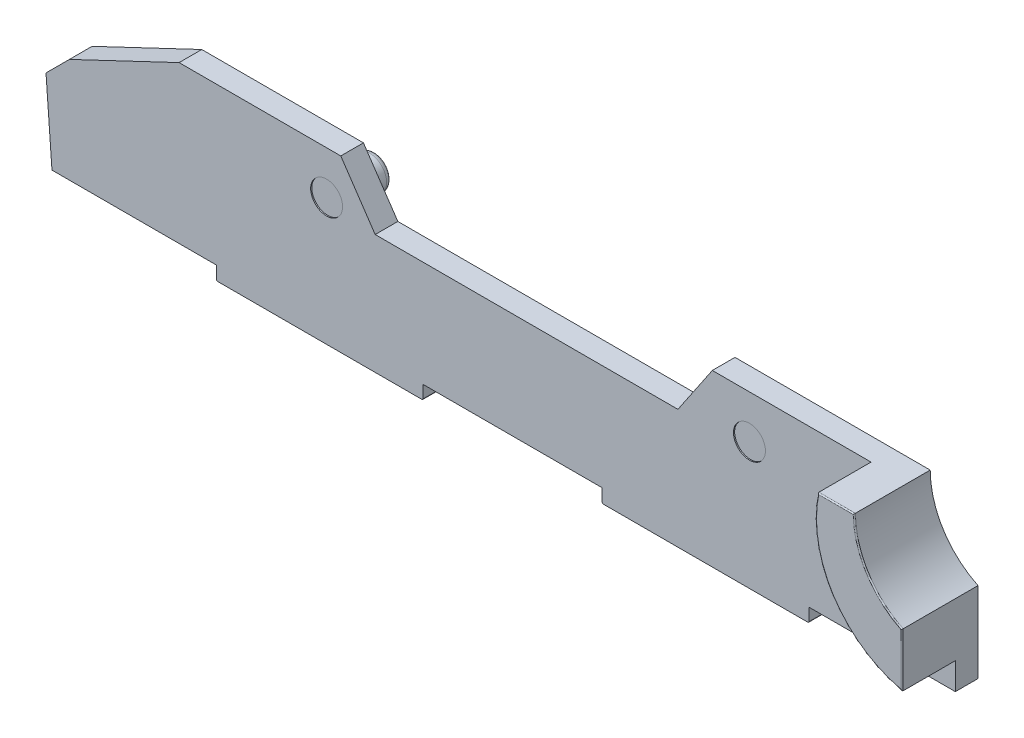
SolidWorks part; units mm, degrees
ref_plane "Front Plane" through (0, 0, 0) normal (0, 0, 1) x (1, 0, 0)
ref_plane "Top Plane" through (0, 0, 0) normal (0, 1, 0) x (1, 0, 0)
ref_plane "Right Plane" through (0, 0, 0) normal (1, 0, 0) x (0, 0, -1)
sketch "Sketch1" plane through (0, 0, 0) normal (0, 0, 1) x (1, 0, 0)
  line L1 (0, 0) -> (79.73, 0)
  line L2 (0, 0) -> (-0.5269, 7.1672)
  line L3 (-0.5269, 7.1672) -> (1.5378, 9.2319)
  line L4 (1.5378, 9.2319) -> (11.22, 13.83)
  line L5 (25.49, 0) -> (25.49, 13.83) construction
  line L6 (25.49, 13.83) -> (11.22, 13.83)
  line L7 (0, 0) -> (0, 10.43) construction
  line L9 (15.389, 13.83) -> (15.389, 9.34) construction
  line L10 (25.49, 13.83) -> (28.5258, 9.34)
  line L11 (15.389, 9.34) -> (39.4066, 9.34) construction
  line L12 (55.2458, 9.34) -> (58.2817, 13.83)
  line L13 (25.49, 13.83) -> (63.2386, 13.83) construction
  line L14 (58.2817, 13.83) -> (75.5117, 13.83)
  line L15 (79.73, 0) -> (79.73, 7.11)
  line L16 (28.5258, 9.34) -> (55.2458, 9.34)
  arc A0 (75.5117, 13.83) -> (79.73, 7.11) centre (82.9735, 13.83) ccw
  dimension "D1" = 79.73
  dimension "D2" = 2.92
  dimension "D4" = 5.42
  dimension "D5" = 13.83
  dimension "D6" = 25.49
  dimension "D7" = 14.27
  dimension "D8" = 10.43
  dimension "D9" = 26.72
  dimension "D10" = 5.42
  dimension "D11" = 17.23
  dimension "D12" = 7.11
  dimension "D13" = 4.49
extrude "Boss-Extrude1" add sketch "Sketch1" along normal blind 2
sketch "Sketch2" plane through (0, 0, 0) normal (0, -1, 0) x (1, 0, 0)
  line L0 (0, 2) -> (14.5, 2) construction
  line L1 (0, 2) -> (79.73, 2) construction
  line L2 (14.5, 2) -> (32.75, 2)
  line L3 (14.5, 2) -> (14.5, 0.8)
  line L4 (32.75, 2) -> (32.75, 0.8)
  line L5 (32.75, 0.8) -> (14.5, 0.8)
  dimension "D1" = 14.5
  dimension "D2" = 18.25
  dimension "D3" = 1.2
extrude "Boss-Extrude2" add sketch "Sketch2" along normal blind 1.2
sketch "Sketch3" plane through (0, 0, 0) normal (0, -1, 0) x (1, 0, 0)
  line L1 (32.75, 2) -> (79.73, 2) construction
  line L3 (48.56, 2) -> (66.81, 2)
  line L4 (48.56, 2) -> (48.56, 0.8)
  line L5 (66.81, 2) -> (66.81, 0.8)
  line L6 (66.81, 0.8) -> (48.56, 0.8)
  dimension "D2" = 18.25
  dimension "D3" = 1.2
extrude "Boss-Extrude3" add sketch "Sketch3" along normal blind 1.2
fillet "Fillet1" radius 0.1 1 edges at (66.81, -1.2, 1.4)
fillet "Fillet2" radius 0.1 1 edges at (48.56, -1.2, 1.4)
fillet "Fillet3" radius 0.1 1 edges at (32.75, -1.2, 1.4)
fillet "Fillet4" radius 0.1 1 edges at (14.5, -1.2, 1.4)
sketch "Sketch4" plane through (0, 0, 2) normal (0, 0, 1) x (1, 0, 0)
  line L0 (25.49, 13.83) -> (11.22, 13.83) construction
  line L1 (28.5258, 9.34) -> (25.49, 13.83) construction
  line L2 (75.5117, 13.83) -> (58.2817, 13.83) construction
  line L3 (58.2817, 13.83) -> (55.2458, 9.34) construction
  circle A0 centre (24.2395, 10.02) radius 1.41
  circle A1 centre (61.5602, 10.02) radius 1.41
  dimension "D1" = 2.82
  dimension "D2" = 3.81
  dimension "D4" = 2.82
  dimension "D3" = 3.17
  dimension "D5" = 3.81
  dimension "D6" = 4.85
extrude "Cut-Extrude1" cut sketch "Sketch4" against normal blind 0.1
sketch "Sketch5" plane through (0, 0, 2) normal (0, 0, 1) x (1, 0, 0)
  line L0 (75.5117, 13.83) -> (72.2917, 13.83)
  line L1 (75.5117, 13.83) -> (58.2817, 13.83) construction
  line L2 (79.73, 7.11) -> (79.73, 2.37)
  line L3 (79.73, 0) -> (79.73, 7.11) construction
  arc A0 (79.73, 2.37) -> (72.2917, 13.83) centre (81.7408, 11.8192) cw
  arc A1 (75.5117, 13.83) -> (79.73, 7.11) centre (82.9735, 13.83) ccw
  dimension "D1" = 3.22
  dimension "D2" = 4.74
extrude "Boss-Extrude4" add sketch "Sketch5" along normal blind 4.7
fillet "Fillet5" radius 0.1 4 edges at (79.73, 4.74, 6.7) (73.6374, 6.5595, 6.7) (73.9017, 13.83, 6.7) (76.6536, 9.8629, 6.7)
shell "Shell1" thickness 1.2 removed face at (37.6162, 8.8093, 0)
sketch "Sketch6" plane through (0, 0, 0.8) normal (0, 0, -1) x (-1, 0, 0)
  line L0 (-74.1219, 8.14) -> (-2.143, 8.14)
  line L1 (-2.2398, 8.2368) -> (-0.7101, 6.7072) construction
  line L2 (-2.143, 8.14) -> (-0.943, 6.94)
  line L3 (-74.8287, 6.94) -> (-0.943, 6.94)
  line L4 (-74.1219, 8.14) -> (-74.8287, 6.94)
  arc A0 (-78.53, 3.9913) -> (-73.319, 12.63) centre (-81.7408, 11.8192) ccw construction
  arc A1 (-78.53, 3.9913) -> (-73.319, 12.63) centre (-81.7408, 11.8192) ccw construction
extrude "Boss-Extrude5" add sketch "Sketch6" along normal blind 0.5
sketch "Sketch7" plane through (0, 0, 0.7) normal (0, 0, -1) x (-1, 0, 0)
  circle A0 centre (-61.5602, 10.02) radius 1.5
  dimension "D1" = 3
extrude "Boss-Extrude6" add sketch "Sketch7" along normal blind 3
fillet "Fillet6" radius 0.5 1 edges at (60.0602, 10.02, -2.3)
sketch "Sketch8" plane through (0, 0, -2.3) normal (0, 0, -1) x (-1, 0, 0)
  circle A0 centre (-61.5602, 10.02) radius 0.5
  dimension "D1" = 1
extrude "Cut-Extrude2" cut sketch "Sketch8" against normal blind 3
sketch "Sketch9" plane through (0, 0, 0.7) normal (0, 0, -1) x (-1, 0, 0)
  circle A0 centre (-24.2395, 10.02) radius 1.5
  dimension "D1" = 3
extrude "Boss-Extrude7" add sketch "Sketch9" along normal blind 3
fillet "Fillet7" radius 0.5 1 edges at (22.7395, 10.02, -2.3)
sketch "Sketch10" plane through (0, 0, -2.3) normal (0, 0, -1) x (-1, 0, 0)
  circle A0 centre (-24.2395, 10.02) radius 0.5
extrude "Cut-Extrude3" cut sketch "Sketch10" against normal blind 3
fillet "Fillet10" radius 2 1 edges at (73.4122, 10.3299, 0.8)
fillet "Fillet11" radius 2 1 edges at (76.469, 5.2016, 0.8)
